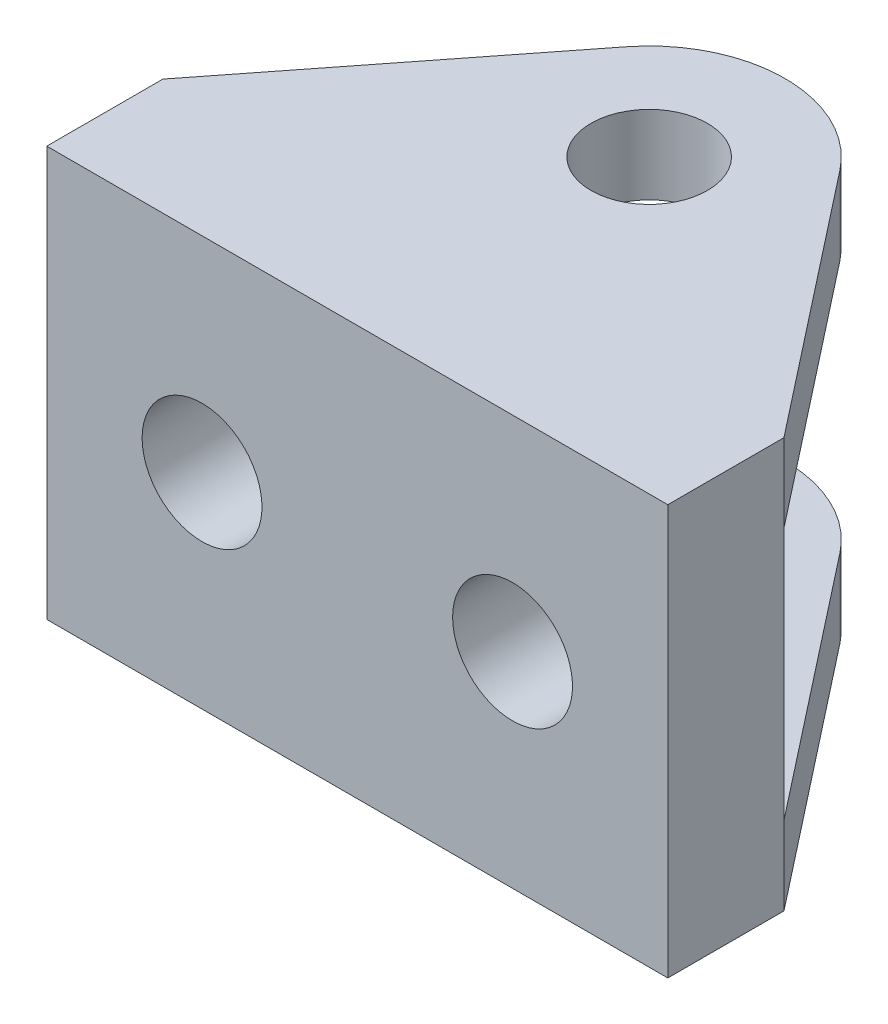
SolidWorks part; units mm, degrees
ref_plane "Front Plane" through (0, 0, 0) normal (0, 0, 1) x (1, 0, 0)
ref_plane "Top Plane" through (0, 0, 0) normal (0, 1, 0) x (1, 0, 0)
ref_plane "Right Plane" through (0, 0, 0) normal (1, 0, 0) x (0, 0, -1)
sketch "Sketch1" plane through (0, 0, 0) normal (0, 1, 0) x (1, 0, 0)
  line L0 (0, 0) -> (50.8, 0)
  line L1 (50.8, 0) -> (50.8, 9.4996)
  line L2 (0, 0) -> (0, 9.4996)
  line L3 (50.8, 9.4996) -> (34.1436, 30.7344)
  line L4 (0, 9.4996) -> (16.6564, 30.7344)
  line L5 (25.4, 0) -> (25.4, 43.8119) construction
  circle A0 centre (25.4, 23.876) radius 4.7625
  arc A1 (34.1436, 30.7344) -> (16.6564, 30.7344) centre (25.4, 23.876) ccw
  dimension "D4" = 6.35
  dimension "D5" = 9.525
  dimension "D1" = 23.876
  dimension "D2" = 50.8
  dimension "D3" = 9.4996
extrude "Boss-Extrude1" add sketch "Sketch1" along normal blind 33.528
sketch "Sketch2" plane through (50.8, 0, 0) normal (1, 0, 0) x (0, 0, -1)
  line L0 (9.4996, 16.764) -> (9.4996, 27.1145)
  line L1 (9.4996, 33.528) -> (9.4996, 0) construction
  line L2 (9.4996, 27.1145) -> (34.9885, 27.1145)
  line L3 (9.4996, 16.764) -> (9.4996, 6.4135)
  line L4 (9.4996, 6.4135) -> (34.9885, 6.4135)
  line L5 (34.9885, 6.4135) -> (34.9885, 27.1145)
  line L6 (34.9885, 0) -> (34.9885, 33.528) construction
  dimension "D1" = 20.701
extrude "Cut-Extrude1" cut sketch "Sketch2" against normal through all
sketch "Sketch3" plane through (0, 0, -9.4996) normal (0, 0, -1) x (-1, 0, 0)
  line L0 (-50.8, 16.764) -> (0, 16.764) construction
  line L1 (-50.8, 27.1145) -> (-50.8, 6.4135) construction
  line L2 (0, 27.1145) -> (0, 6.4135) construction
  line L3 (-25.4, 16.764) -> (-25.4, 27.1145) construction
  line L4 (0, 27.1145) -> (-50.8, 27.1145) construction
  circle A0 centre (-38.1, 16.764) radius 4.9022
  circle A1 centre (-12.7, 16.764) radius 4.9022
  dimension "D3" = 9.8044
  dimension "D4" = 9.8044
  dimension "D1" = 12.7
  dimension "D2" = 12.7
extrude "Cut-Extrude2" cut sketch "Sketch3" against normal up to surface (9.4996 mm away) up to face at (25.4, 16.764, 0)
ref_axis "Axis1" through (25.4, 82.5272, -23.876) along (0, -1, 0)
ref_plane "Plane1" through (0, 16.764, 0) normal (0, -1, 0) x (-1, 0, 0)
ref_point "Point2"
equation "\"1inch\"=62.1211"
